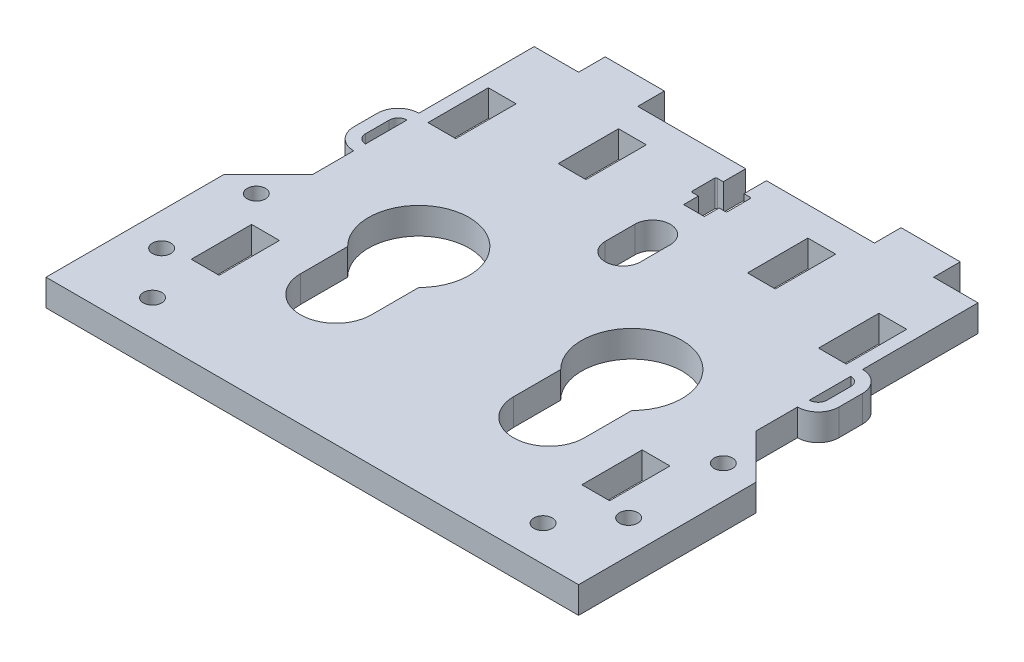
SolidWorks part; units mm, degrees
ref_plane "Front Plane" through (0, 0, 0) normal (0, 0, 1) x (1, 0, 0)
ref_plane "Top Plane" through (0, 0, 0) normal (0, 1, 0) x (1, 0, 0)
ref_plane "Right Plane" through (0, 0, 0) normal (1, 0, 0) x (0, 0, -1)
sketch "Sketch1" plane through (0, 0, 0) normal (0, 1, 0) x (1, 0, 0)
  line L1 (-37.5, 37.5) -> (37.5, 37.5)
  line L2 (-37.5, 37.5) -> (-37.5, -37.5)
  line L3 (-37.5, -37.5) -> (37.5, -37.5)
  line L4 (37.5, 37.5) -> (37.5, -37.5)
  line L5 (-37.5, 37.5) -> (37.5, -37.5) construction
  line L6 (-37.5, -37.5) -> (37.5, 37.5) construction
  point P0 (0, 0)
  dimension "D1" = 75
  dimension "D2" = 75
extrude "MainShape" add sketch "Sketch1" along normal blind 4.5
sketch "Sketch2" plane through (0, 4.5, 0) normal (0, 1, 0) x (1, 0, 0)
  line L0 (0, -37.5) -> (0, 37.5) construction
  line L1 (-37.5, -37.5) -> (37.5, -37.5) construction
  line L2 (37.5, 37.5) -> (-37.5, 37.5) construction
  line L4 (-5, 42) -> (5, 42)
  line L5 (-5, 42) -> (-5, 33)
  line L6 (-5, 33) -> (5, 33)
  line L7 (5, 42) -> (5, 33)
  line L8 (-5, 42) -> (5, 33) construction
  line L9 (-5, 33) -> (5, 42) construction
  dimension "D1" = 10
  dimension "D2" = 4.5
extrude "Tab1" [suppressed] add sketch "Sketch2" against normal through all
sketch "Sketch4" [suppressed] plane through (0, 4.5, 0) normal (0, 1, 0) x (1, 0, 0)
  line L0 (0, 42) -> (0, -37.5) construction
  line L1 (5, 42) -> (-5, 42) construction
  line L2 (-47.5, -37.5) -> (47.5, -37.5) construction
  line L3 (-40, 37.5) -> (-40, 27) construction
  line L4 (-5, 37.5) -> (-47.5, 37.5) construction
  line L5 (-38.25, 27) -> (-41.75, 27) construction
  line L6 (-41.75, 27) -> (-41.75, 37.5) construction
  line L7 (-38.25, 27) -> (-41.75, 27)
  line L8 (-41.75, 27) -> (-41.75, 29.5)
  line L9 (-41.75, 29.5) -> (-42.75, 29.5)
  line L10 (-43, 29.75) -> (-43, 33.45)
  line L11 (-42.75, 33.7) -> (-41.75, 33.7)
  line L12 (-41.75, 33.7) -> (-41.75, 37.5)
  line L13 (-41.75, 37.5) -> (-38.25, 37.5)
  line L14 (-38.25, 27) -> (-38.25, 37.5) construction
  line L15 (-38.25, 33.7) -> (-38.25, 37.5)
  line L16 (-37.25, 33.7) -> (-38.25, 33.7)
  line L17 (-37, 29.75) -> (-37, 33.45)
  line L18 (-38.25, 29.5) -> (-37.25, 29.5)
  line L19 (-38.25, 27) -> (-38.25, 29.5)
  line L20 (38.25, 27) -> (38.25, 37.5) construction
  line L21 (41.75, 27) -> (41.75, 37.5) construction
  line L22 (38.25, 27) -> (41.75, 27) construction
  line L23 (40, 37.5) -> (40, 27) construction
  line L24 (38.25, 27) -> (38.25, 29.5)
  line L25 (38.25, 29.5) -> (37.25, 29.5)
  line L26 (37, 29.75) -> (37, 33.45)
  line L27 (37.25, 33.7) -> (38.25, 33.7)
  line L28 (38.25, 33.7) -> (38.25, 37.5)
  line L29 (41.75, 37.5) -> (38.25, 37.5)
  line L30 (41.75, 33.7) -> (41.75, 37.5)
  line L31 (42.75, 33.7) -> (41.75, 33.7)
  line L32 (43, 29.75) -> (43, 33.45)
  line L33 (41.75, 29.5) -> (42.75, 29.5)
  line L34 (41.75, 27) -> (41.75, 29.5)
  line L35 (38.25, 27) -> (41.75, 27)
  arc A0 (-42.75, 29.5) -> (-43, 29.75) centre (-42.75, 29.75) cw
  arc A1 (-37, 29.75) -> (-37.25, 29.5) centre (-37.25, 29.75) cw
  arc A2 (-37.25, 33.7) -> (-37, 33.45) centre (-37.25, 33.45) cw
  arc A3 (-43, 33.45) -> (-42.75, 33.7) centre (-42.75, 33.45) cw
  arc A4 (43, 33.45) -> (42.75, 33.7) centre (42.75, 33.45) ccw
  arc A5 (37.25, 33.7) -> (37, 33.45) centre (37.25, 33.45) ccw
  arc A6 (37, 29.75) -> (37.25, 29.5) centre (37.25, 29.75) ccw
  arc A7 (42.75, 29.5) -> (43, 29.75) centre (42.75, 29.75) ccw
  point P24 (-43, 29.5)
  point P27 (-37, 29.5)
  point P30 (-37, 33.7)
  point P33 (-43, 33.7)
  point P56 (43, 33.7)
  point P57 (37, 33.7)
  point P58 (37, 29.5)
  point P59 (43, 29.5)
  dimension "D7" = 0.25
  dimension "D1" = 10.5
  dimension "D2" = 1.75
  dimension "D3" = 4.2
  dimension "D4" = 3
  dimension "D5" = 8
  dimension "D6" = 40
extrude "Cut-Extrude2" [suppressed] cut sketch "Sketch4" against normal through all
sketch "Sketch5" plane through (0, 4.5, 0) normal (0, 1, 0) x (1, 0, 0)
  line L0 (0, -37.5) -> (0, 37.5) construction
  line L1 (-37.5, -37.5) -> (37.5, -37.5) construction
  line L3 (33, 37.5) -> (33, -37.5) construction
  line L4 (37.5, 37.5) -> (-37.5, 37.5) construction
  line L5 (-33, 37.5) -> (-33, -37.5) construction
  line L6 (30.65, 27.6) -> (35.35, 27.6)
  line L7 (30.65, 27.6) -> (30.65, 17.4)
  line L8 (30.65, 17.4) -> (35.35, 17.4)
  line L9 (35.35, 27.6) -> (35.35, 17.4)
  line L10 (30.65, 27.6) -> (35.35, 17.4) construction
  line L11 (30.65, 17.4) -> (35.35, 27.6) construction
  line L12 (-30.65, 17.4) -> (-35.35, 27.6) construction
  line L13 (-30.65, 27.6) -> (-35.35, 17.4) construction
  line L14 (-35.35, 27.6) -> (-35.35, 17.4)
  line L15 (-30.65, 17.4) -> (-35.35, 17.4)
  line L16 (-30.65, 27.6) -> (-30.65, 17.4)
  line L17 (-30.65, 27.6) -> (-35.35, 27.6)
  line L18 (-37.5, 2.5) -> (37.5, 2.5) construction
  line L19 (-37.5, 37.5) -> (-37.5, -37.5) construction
  line L20 (37.5, -37.5) -> (37.5, 37.5) construction
  line L21 (-30.65, -22.6) -> (-35.35, -12.4) construction
  line L22 (-30.65, -12.4) -> (-35.35, -22.6) construction
  line L23 (30.65, -12.4) -> (35.35, -22.6) construction
  line L24 (30.65, -22.6) -> (35.35, -12.4) construction
  line L25 (-30.65, -22.6) -> (-35.35, -22.6)
  line L26 (-30.65, -22.6) -> (-30.65, -12.4)
  line L27 (-30.65, -12.4) -> (-35.35, -12.4)
  line L28 (-35.35, -22.6) -> (-35.35, -12.4)
  line L29 (35.35, -22.6) -> (35.35, -12.4)
  line L30 (30.65, -12.4) -> (35.35, -12.4)
  line L31 (30.65, -22.6) -> (30.65, -12.4)
  line L32 (30.65, -22.6) -> (35.35, -22.6)
  line L33 (-30.65, 27.6) -> (-35.35, 17.4) construction
  line L34 (-37.5, 37.5) -> (37.5, 37.5) construction
  line L35 (37.5, 37.5) -> (-37.5, 37.5) construction
  point P10 (33, 22.5)
  point P21 (-33, 22.5)
  point P36 (-33, -17.5)
  point P37 (33, -17.5)
  dimension "D1" = 33
  dimension "D2" = 10.2
  dimension "D3" = 4.7
  dimension "D4" = 15
  dimension "D5" = 40
extrude "Cut-Extrude3" cut sketch "Sketch5" against normal through all
sketch "Sketch6" plane through (0, 4.5, 0) normal (0, 1, 0) x (1, 0, 0)
  line L0 (-18, -37.5) -> (-18, 28) construction
  line L1 (-24, -15.5) -> (-24, -7.5208)
  line L3 (-37.5, -15.5) -> (37.5, -15.5) construction
  line L4 (-37.5, 37.5) -> (-37.5, -37.5) construction
  line L5 (37.5, -37.5) -> (37.5, 37.5) construction
  line L6 (37.5, 37.5) -> (-37.5, 37.5) construction
  line L7 (-37.5, -37.5) -> (37.5, -37.5) construction
  line L8 (-12, -15.5) -> (-12, -7.5208)
  line L9 (-37.5, 37.5) -> (37.5, 37.5) construction
  arc A0 (-24, -15.5) -> (-12, -15.5) centre (-18, -15.5) ccw
  arc A2 (-12, -7.5208) -> (-24, -7.5208) centre (-18, -1.5) ccw
  dimension "D1" = 12
  dimension "D6" = 8.5
  dimension "D2" = 53
  dimension "D3" = 0
  dimension "D5" = 0
  dimension "D7" = 14
  dimension "D4" = 18
extrude "Cut-Extrude4" cut sketch "Sketch6" against normal through all
sketch "Sketch13" plane through (0, 4.5, 0) normal (0, 1, 0) x (1, 0, 0)
  line L0 (-37.5, 0) -> (-45, -7.5)
  line L1 (-37.5, 37.5) -> (-37.5, -37.5) construction
  line L2 (-45, -7.5) -> (-45, -37.5)
  line L3 (-45, -37.5) -> (-37.5, -37.5)
  line L4 (-37.5, -37.5) -> (-37.5, 0)
  line L5 (0, 37.5) -> (0, -37.5) construction
  line L6 (37.5, 37.5) -> (-37.5, 37.5) construction
  line L7 (-37.5, -37.5) -> (37.5, -37.5) construction
  line L8 (37.5, -37.5) -> (37.5, 0)
  line L9 (45, -37.5) -> (37.5, -37.5)
  line L10 (45, -7.5) -> (45, -37.5)
  line L11 (37.5, 0) -> (45, -7.5)
  line L12 (-37.5, -37.5) -> (-37.5, 0)
  line M23 (37.5, -37.5) -> (37.5, 37.5)
  line M25 (-37.5, 37.5) -> (-37.5, -37.5)
  dimension "D1" = 45
  dimension "D2" = 30
extrude "Boss-Extrude2" add sketch "Sketch13" against normal through all contours L2 L3 L0 M25 | L11 L9 L10 M23 region at (-41.1111, 4.5, 20.5556) region at (41.1111, 4.5, 20.5556)
sketch "Sketch8" plane through (0, 4.5, 0) normal (0, 1, 0) x (1, 0, 0)
  line L0 (-18, -9.5) -> (-18, -21.5) construction
  line L1 (-18, -15.5) -> (-39.46, -15.5) construction
  line L2 (-39.46, -23.5) -> (-39.46, -7.5) construction
  line L3 (-18, -21.5) -> (-18, -9.5) construction
  circle A0 centre (-39.46, -7.5) radius 1.55
  circle A1 centre (-18, -15.5) radius 6 construction
  circle A2 centre (-39.46, -23.5) radius 1.55
  dimension "D3" = 3.1
  dimension "D1" = 0
  dimension "D2" = 8
  dimension "D4" = 21.46
extrude "Cut-Extrude6" cut sketch "Sketch8" against normal through all
mirror "Mirror1" about plane through (0, 0, 0) normal (1, 0, 0) of "Cut-Extrude6", "Cut-Extrude4"
sketch "Sketch11" plane through (0, 4.5, 0) normal (0, 1, 0) x (1, 0, 0)
  line L0 (0, 37.5) -> (0, -37.5) construction
  line L1 (37.5, 37.5) -> (-37.5, 37.5) construction
  line L2 (-45, -37.5) -> (45, -37.5) construction
  line L3 (-25, 42) -> (-25, 37.5) construction
  line L4 (-30, 37.5) -> (-20, 37.5)
  line L5 (-30, 37.5) -> (-30, 42)
  line L6 (-30, 42) -> (-20, 42)
  line L7 (-20, 37.5) -> (-20, 42)
  line L8 (25, 42) -> (25, 37.5) construction
  line L9 (20, 37.5) -> (20, 42)
  line L10 (30, 42) -> (20, 42)
  line L11 (30, 37.5) -> (30, 42)
  line L12 (30, 37.5) -> (20, 37.5)
  dimension "D1" = 10
  dimension "D2" = 4.5
  dimension "D3" = 25
extrude "RearTabs" add sketch "Sketch11" against normal through all
sketch "Sketch12" plane through (0, 4.5, 0) normal (0, 1, 0) x (1, 0, 0)
  line L0 (0, 0) -> (0, 37.5) construction
  line L1 (20, 37.5) -> (-20, 37.5) construction
  line L2 (1.75, 37.5) -> (-1.75, 37.5)
  line L3 (-1.75, 37.5) -> (-1.75, 33.7)
  line L4 (-1.75, 33.7) -> (-2.75, 33.7)
  line L5 (-3, 33.45) -> (-3, 29.75)
  line L6 (-2.75, 29.5) -> (-1.75, 29.5)
  line L7 (-1.75, 29.5) -> (-1.75, 27)
  line L8 (-1.75, 27) -> (1.75, 27)
  line L9 (1.75, 29.5) -> (1.75, 27)
  line L10 (2.75, 29.5) -> (1.75, 29.5)
  line L11 (3, 33.45) -> (3, 29.75)
  line L12 (1.75, 33.7) -> (2.75, 33.7)
  line L13 (1.75, 37.5) -> (1.75, 33.7)
  arc A0 (-3, 29.75) -> (-2.75, 29.5) centre (-2.75, 29.75) ccw
  arc A1 (-2.75, 33.7) -> (-3, 33.45) centre (-2.75, 33.45) ccw
  arc A2 (2.75, 33.7) -> (3, 33.45) centre (2.75, 33.45) cw
  arc A3 (3, 29.75) -> (2.75, 29.5) centre (2.75, 29.75) cw
  point P14 (-3, 29.5)
  point P17 (-3, 33.7)
  point P25 (0, 27)
  point P28 (3, 33.7)
  point P29 (3, 29.5)
  dimension "D1" = 10.5
  dimension "D5" = 8
  dimension "D6" = 0.25
  dimension "D2" = 4.2
  dimension "D3" = 3
  dimension "D4" = 1.75
extrude "FrontScrewSlot" cut sketch "Sketch12" against normal through all
sketch "Sketch14" plane through (0, 4.5, 0) normal (0, 1, 0) x (1, 0, 0)
  line L0 (-33, 27.6) -> (-33, -37.5) construction
  line L1 (-30.65, 27.6) -> (-35.35, 27.6) construction
  line L2 (-45, -37.5) -> (45, -37.5) construction
  line L3 (-30, 37.5) -> (-37.5, 37.5) construction
  line L4 (0, 0) -> (0, -37.5) construction
  line L5 (33, 27.6) -> (33, -37.5) construction
  line L6 (-33, 27.6) -> (-33, -37.5) construction
  circle A0 centre (-33, -31.5) radius 1.55
  circle A1 centre (33, -31.5) radius 1.55
  dimension "D2" = 3.1
  dimension "D1" = 69
extrude "BraceScrews" cut sketch "Sketch14" against normal through all
sketch "Sketch15" plane through (0, 4.5, 0) normal (0, 1, 0) x (1, 0, 0)
  line L0 (0, -37.5) -> (0, 27) construction
  line L1 (-45, -37.5) -> (45, -37.5) construction
  line L2 (-1.75, 27) -> (1.75, 27) construction
  line L3 (16, 27.5) -> (-16, 27.5) construction
  line L4 (-1.75, 37.5) -> (-20, 37.5) construction
  line L5 (-18.35, 32.6) -> (-13.65, 32.6)
  line L6 (-18.35, 32.6) -> (-18.35, 22.4)
  line L7 (-18.35, 22.4) -> (-13.65, 22.4)
  line L8 (-13.65, 32.6) -> (-13.65, 22.4)
  line L9 (-18.35, 32.6) -> (-13.65, 22.4) construction
  line L10 (-18.35, 22.4) -> (-13.65, 32.6) construction
  line L11 (18.35, 22.4) -> (13.65, 32.6) construction
  line L12 (18.35, 32.6) -> (13.65, 22.4) construction
  line L13 (13.65, 32.6) -> (13.65, 22.4)
  line L14 (18.35, 22.4) -> (13.65, 22.4)
  line L15 (18.35, 32.6) -> (18.35, 22.4)
  line L16 (18.35, 32.6) -> (13.65, 32.6)
  point P19 (0, 27.5)
  dimension "D1" = 16
  dimension "D2" = 4.7
  dimension "D3" = 10.2
  dimension "D4" = 10
extrude "FanTabs" cut sketch "Sketch15" against normal through all
sketch "Sketch16" plane through (0, 4.5, 0) normal (0, 1, 0) x (1, 0, 0)
  line L0 (0, 0) -> (0, 27) construction
  line L1 (-1.75, 27) -> (1.75, 27) construction
  line L2 (0, 20) -> (0, 15) construction
  line L3 (3, 20) -> (3, 15)
  line L4 (-3, 20) -> (-3, 15)
  arc A0 (3, 20) -> (-3, 20) centre (0, 20) ccw
  arc A1 (-3, 15) -> (3, 15) centre (0, 15) ccw
  point P7 (0, 17.5)
  dimension "D1" = 3
  dimension "D2" = 20
  dimension "D3" = 5
extrude "WiringSlot" cut sketch "Sketch16" against normal through all
sketch "Sketch17" plane through (0, 4.5, 0) normal (0, 1, 0) x (1, 0, 0)
  line L0 (-37.5, 14.5) -> (-37.5, 10.5) construction
  line L3 (-37.5, 37.5) -> (-37.5, 0) construction
  line L4 (-36, 14.5) -> (-36, 10.5)
  line L5 (-39, 14.5) -> (-39, 10.5)
  line L6 (-37.5, 14.5) -> (-37.5, 10.5) construction
  line L7 (-34, 14.5) -> (-34, 10.5)
  line L8 (-41, 14.5) -> (-41, 10.5)
  line L9 (-41, 12.5) -> (-37.5, 12.5) construction
  line L10 (0, 0) -> (0, -12.1805) construction
  arc A0 (-36, 14.5) -> (-39, 14.5) centre (-37.5, 14.5) ccw
  arc A1 (-39, 10.5) -> (-36, 10.5) centre (-37.5, 10.5) ccw
  arc A2 (-34, 14.5) -> (-41, 14.5) centre (-37.5, 14.5) ccw
  arc A3 (-41, 10.5) -> (-34, 10.5) centre (-37.5, 10.5) ccw
  point P4 (-37.5, 12.5)
  point P10 (-37.5, 12.5)
  dimension "D4" = 4
  dimension "D5" = 25
  dimension "D1" = 0
  dimension "D2" = 2
  dimension "D3" = 1.5
extrude "Boss-Extrude3" add sketch "Sketch17" against normal through all
mirror "Mirror2" about plane through (0, 0, 0) normal (1, 0, 0) of "Boss-Extrude3"
equation "\"X-ROD-SPACING\"=45"
equation "\"Y-ROD-SPACING\"=75"
equation "\"Z-ROD-SPACING\"=17.5"
equation "\"Y-BED-OFFSET\"=2"
equation "\"Y-BED-ROD-INSET\"=3.5"
equation "\"Y-BED-SCREW-SPACING\"=209"
equation "\"Y-BED-SCREW-CUTOUT-SLOT-HEIGHT\"=2"
equation "\"T-SLOT-NUT-FILLET-RADIUS\"=0.25"
equation "\"T-SLOT-SCREW-SHAFT-RADIUS\"=1.75"
equation "\"T-SLOT-SCREW-SHAFT-CUTOUT-LENGTH\"=10.5"
equation "\"T-SLOT-NUT-DEPTH\"=4.2"
equation "\"T-SLOT-NUT-WIDTH\"=3"
equation "\"T-SLOT-NUT-END-DISTANCE\"=8"
equation "\"ACRYLIC-THICKNESS\"=10"
equation "\"ACRYLIC-THICKNESS2\"=4.5"
equation "\"ACRYLIC-TAB-CUTOUT-SIZE\"=\"ACRYLIC-THICKNESS\"+\"ACRYLIC-TAB-TOLERANCE\"*2"
equation "\"ACRYLIC-TAB-WIDTH\"=\"ACRYLIC-THICKNESS\""
equation "\"ACRYLIC-M3-HOLE\"=3.1"
equation "\"SMOOTHROD-CAP-SCREW-DISTANCE\"=20"
equation "\"FRAME-WIDTH-INNER\"=370"
equation "\"NEMA17-HOLE-SPACING\"=31"
equation "\"NEMA17-CENTRAL-CUTOUT\"=22.5"
equation "\"Z-BRACKET-REACH\"=55"
equation "\"Z-ROD-INSET\"=16"
equation "\"TOP-BRACKET-SPACING\"=40"
equation "\"SMOOTHROD-X-LENGTH\"=350"
equation "\"SMOOTHROD-Y-LENGTH\"=350"
equation "\"SMOOTHROD-Z-LENGTH\"=350"
equation "\"SMOOTHROD-TIGHTENING-HEADROOM\"=.25"
equation "\"LEADSCREW-Z-LENGTH\"=300"
equation "\"SCREW-LENGTH-FRAME\"=\"ACRYLIC-THICKNESS\" + 10"
equation "\"SCREW-LENGTH-MOTOR\"=\"ACRYLIC-THICKNESS\" + 5"
equation "\"SCREW-LENGTH-EXTRUDER\"=28"
equation "\"SCREW-HEAD-RADIUS\"=6"
equation "\"PRINTED-X-SMOOTHROD-DIAMETER\"=8.2"
equation "\"PRINTED-X-SMOOTHROD-CUTOUT\"=10"
equation "\"PRINTED-X-BASE-HEIGHT\"=10"
equation "\"PRINTED-LM8UU-CUTOUT-SIZE\"=15.25"
equation "\"PRINTED-LM8UU-CUTOUT-LENGTH\"=24.5"
equation "\"PRINTED-X-IDLER-HEIGHT\"=16"
equation "\"PSU-MOUNTING-WIDTH\"=95"
equation "\"PSU-MOUNTING-HEIGHT\"=177"
equation "\"Y-BELT-TO-ROD-DISTANCE\"=20"
equation "\"SPOOL-HOLDER-ROD-SPACING\"=150"
equation "\"ACRYLIC-X-CARRIAGE-WIDTH\"=55"
equation "\"ACRYLIC-X-CARRIAGE-HEIGHT\"=75"
equation "\"ACRYLIC-X-CARRIAGE-SCREW-SPACING-X\"=15"
equation "\"ACRYLIC-X-CARRIAGE-SCREW-SPACING-Y\"=33"
equation "\"ACRYLIC-X-CARRIAGE-CENTER-TAB-SPACING\"=14"
equation "\"D1@MainShape\" = \"ACRYLIC-THICKNESS2\""
equation "\"D1@Sketch2\"=\"ACRYLIC-TAB-WIDTH\""
equation "\"D2@Sketch2\"=\"ACRYLIC-THICKNESS2\""
equation "\"D1@Sketch4\"=\"T-SLOT-SCREW-SHAFT-CUTOUT-LENGTH\""
equation "\"D2@Sketch4\"=\"T-SLOT-SCREW-SHAFT-RADIUS\""
equation "\"D3@Sketch4\"=\"T-SLOT-NUT-DEPTH\""
equation "\"D4@Sketch4\"=\"T-SLOT-NUT-WIDTH\""
equation "\"D5@Sketch4\"=\"T-SLOT-NUT-END-DISTANCE\""
equation "\"D7@Sketch4\"=\"T-SLOT-NUT-FILLET-RADIUS\""
equation "\"ACRYLIC-X-CARRIAGE-EXTRUDER-SHELF-DEPTH\"=\"ACRYLIC-X-CARRIAGE-EXTRUDER-OFFSET\" + 28"
equation "\"ACRYLIC-X-CARRIAGE-LM8UU-CUTOUT-WIDTH\"=24.25"
equation "\"ACRYLIC-X-CARRIAGE-EXTRUDER-BRACE-SPACING\"=23"
equation "\"ACRYLIC-X-CARRIAGE-EXTRUDER-BRACE-TAB-OFFSET\"=20"
equation "\"ACRYLIC-X-CARRIAGE-EXTRUDER-BRACE-HEIGHT\"=35"
equation "\"ACRYLIC-X-CARRIAGE-EXTRUDER-BRACE-SCREW-SPACING\"=22"
equation "\"D2@Sketch5\"=\"ACRYLIC-TAB-CUTOUT-SIZE\""
equation "\"D3@Sketch5\"=\"ACRYLIC-THICKNESS2\"+\"ACRYLIC-TAB-TOLERANCE\"*2"
equation "\"D3@Sketch8\"=\"ACRYLIC-M3-HOLE\""
equation "\"ACRYLIC-X-CARRIAGE-EXTRUDER-ANGLE\"=90"
equation "\"ACRYLIC-X-CARRIAGE-EXTRUDER-OFFSET\"=26"
equation "\"ACRYLIC-TAB-TOLERANCE\"=.1"
equation "\"ACRYLIC-X-CARRIAGE-DUAL-WIDTH-MULTIPLIER\"=1.65"
equation "\"ACRYLIC-X-CARRIAGE-DUAL-HOTEND-SPACING\"=42"
equation "\"ACRYLIC-X-CARRIAGE-DUAL-WIDTH\"=75"
equation "\"ACRYLIC-X-CARRIAGE-DUAL-HOTEND-SEPARATION\"=36"
equation "\"ACRYLIC-X-CARRIAGE-DUAL-MOUNT-PLATE-DEPTH\"=75"
equation "\"ACRYLIC-X-CARRIAGE-DUAL-MOUNT-BRACE-WIDTH\"=33"
equation "\"D1@Sketch5\"=\"ACRYLIC-X-CARRIAGE-DUAL-MOUNT-BRACE-WIDTH\""
equation "\"ACRYLIC-X-CARRIAGE-DUAL-MOUNT-SCREW-WIDTH\"=40"
equation "\"D6@Sketch4\"=\"ACRYLIC-X-CARRIAGE-DUAL-MOUNT-SCREW-WIDTH\""
equation "\"D1@Sketch1\"=\"ACRYLIC-X-CARRIAGE-DUAL-WIDTH\""
equation "\"D2@Sketch1\"=\"ACRYLIC-X-CARRIAGE-DUAL-MOUNT-PLATE-DEPTH\""
equation "\"D4@Sketch6\"=\"ACRYLIC-X-CARRIAGE-DUAL-HOTEND-SEPARATION\"/2"
equation "\"D1@Sketch11\"=\"ACRYLIC-TAB-WIDTH\""
equation "\"D2@Sketch11\"=\"ACRYLIC-THICKNESS2\""
equation "\"D1@Sketch12\"=\"T-SLOT-SCREW-SHAFT-CUTOUT-LENGTH\""
equation "\"D2@Sketch12\"=\"T-SLOT-NUT-DEPTH\""
equation "\"D3@Sketch12\"=\"T-SLOT-NUT-WIDTH\""
equation "\"D4@Sketch12\"=\"T-SLOT-SCREW-SHAFT-RADIUS\""
equation "\"D5@Sketch12\"=\"T-SLOT-NUT-END-DISTANCE\""
equation "\"D6@Sketch12\"=\"T-SLOT-NUT-FILLET-RADIUS\""
equation "\"D2@Sketch14\"=\"ACRYLIC-M3-HOLE\""
equation "\"D2@Sketch15\"=\"ACRYLIC-THICKNESS2\"+\"ACRYLIC-TAB-TOLERANCE\"*2"
equation "\"D3@Sketch15\"=\"ACRYLIC-TAB-CUTOUT-SIZE\""
